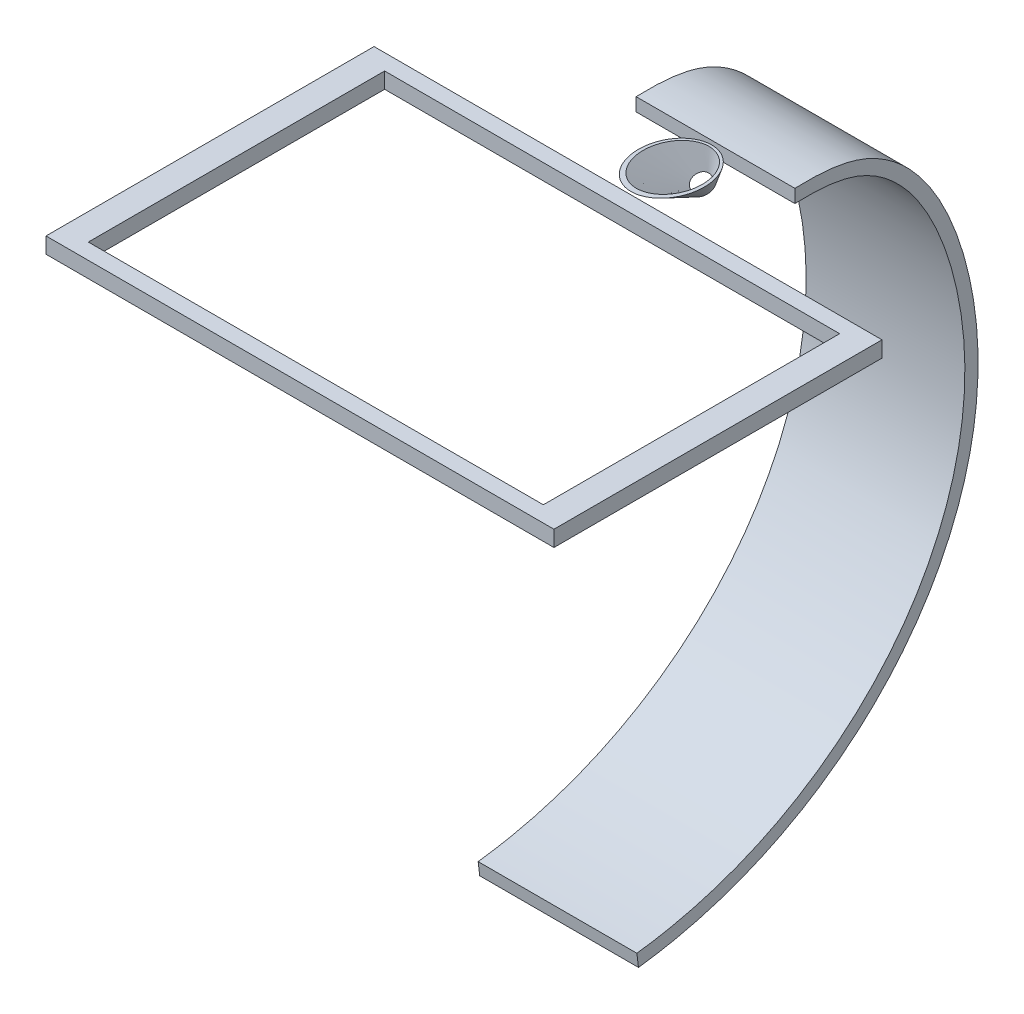
SolidWorks part; units mm, degrees
ref_plane "Front" through (0, 0, 0) normal (0, 0, 1) x (1, 0, 0)
ref_plane "Top" through (0, 0, 0) normal (0, 1, 0) x (1, 0, 0)
ref_plane "Right" through (0, 0, 0) normal (1, 0, 0) x (0, 0, -1)
sketch "Sketch1" plane through (0, 0, 0) normal (0, 1, 0) x (1, 0, 0)
  line L1 (-43, -28) -> (43, -28)
  line L2 (-43, -28) -> (-43, 28)
  line L3 (-43, 28) -> (43, 28)
  line L4 (43, -28) -> (43, 28)
  line L5 (-43, -28) -> (43, 28) construction
  line L6 (-43, 28) -> (43, -28) construction
  line L7 (-48, -31) -> (48, -31)
  line L8 (-48, -31) -> (-48, 31)
  line L9 (-48, 31) -> (48, 31)
  line L10 (48, -31) -> (48, 31)
  line L11 (-48, -31) -> (48, 31) construction
  line L12 (-48, 31) -> (48, -31) construction
  point P0 (0, 0)
  point P6 (0, 0)
  dimension "D1" = 86
  dimension "D2" = 56
  dimension "D3" = 3
  dimension "D4" = 5
extrude "Boss-Extrude1" add sketch "Sketch1" along normal blind 3
sketch "Sketch4" plane through (0, 0, 0) normal (1, 0, 0) x (0, 0, -1)
  line L0 (45.6947, -3.6988) -> (-61.4431, 55.6887) construction
  line L1 (45.6947, -3.6988) -> (-61.4431, 55.6887) construction
  line L2 (32.8171, -9.0552) -> (52.2183, 2.1461) construction
  line L3 (32.8171, -9.0552) -> (52.2183, 2.1461) construction
  line L4 (45.6947, -3.6988) -> (47.8326, 118.7791) construction
  line L5 (45.6947, -3.6988) -> (47.8326, 118.7791) construction
sketch "Sketch5" plane through (0, 0, 0) normal (1, 0, 0) x (0, 0, -1)
  line L0 (45.6947, -3.6988) -> (38.2413, 9.211) construction
  line L1 (32.8171, -9.0552) -> (52.2183, 2.1461) construction
  line L2 (45.6947, -3.6988) -> (-61.4431, 55.6887) construction
  line L3 (43.8581, -2.6807) -> (35.4738, 1.9668)
  line L4 (43.8581, -2.6807) -> (35.4738, 1.9668)
  line L7 (42.8478, -3.264) -> (29.3973, 4.1917)
  line L8 (29.3973, 4.1917) -> (35.4738, 1.9668)
  line L9 (42.8478, -3.264) -> (43.8581, -2.6807)
  line L10 (43.6157, -3.118) -> (32.4355, 3.0793)
  line L11 (43.6157, -3.118) -> (35.2314, 1.5295) construction
  dimension "D1" = 0.5
  dimension "D2" = 0.5
revolve "Revolve4" add sketch "Sketch5" angle 360 about L0 region at (0, 0.2658, -36.9777)
sketch "Sketch6" plane through (0, 0, -31) normal (0, 0, -1) x (-1, 0, 0)
  line L1 (48, 3) -> (-48, 3)
  line L2 (48, 3) -> (48, 16.2937)
  line L3 (48, 16.2937) -> (-48, 16.2937)
  line L4 (-48, 0) -> (48, 0)
  line L5 (48, 0) -> (48, 3)
  line L6 (48, 3) -> (-48, 3)
  line L7 (-48, 3) -> (-48, 0)
  line L8 (-48, 0) -> (48, 0)
  line L9 (48, 0) -> (48, 3)
  line L10 (48, 3) -> (-48, 3)
  line L11 (-48, 3) -> (-48, 0)
  line L12 (-48, 3) -> (-48, 16.2937)
  line M7 (48, 3) -> (-48, 3)
  dimension "D1" = 0
extrude "Cut-Extrude1" cut sketch "Sketch6" along normal through all and the other way through all contours L12 L2 L3 M7 region at (0, 9.6469, -31)
sketch "Sketch7" plane through (0, 0, 0) normal (1, 0, 0) x (0, 0, -1)
  line L13 (32.8171, -19.124) -> (32.8171, -24.1806)
  line L14 (32.8171, -24.1806) -> (37.3171, -21.5825)
  line L15 (37.3171, -21.5825) -> (37.3171, -14.2513)
  line L16 (37.3171, -14.2513) -> (39.4389, -13.0263)
  line L17 (39.4389, -13.0263) -> (38.4389, -11.2943)
  line L18 (38.4389, -11.2943) -> (55.846, -1.2443)
  line L19 (55.846, -1.2443) -> (56.846, -2.9763)
  line L20 (56.846, -2.9763) -> (58.9678, -1.7513)
  line L21 (58.9678, -1.7513) -> (58.5928, -1.1018)
  line L22 (52.2183, 2.1461) -> (32.8171, -9.0552)
  line L23 (32.8171, -9.0552) -> (32.8171, -16.2372)
  line L24 (32.8171, -16.2372) -> (27.8171, -19.124)
  line L25 (27.8171, -19.124) -> (32.8171, -19.124)
  line L26 (32.8171, -19.124) -> (32.8171, -24.1806)
  line L27 (32.8171, -24.1806) -> (37.3171, -21.5825)
  line L28 (37.3171, -21.5825) -> (37.3171, -14.2513)
  line L29 (37.3171, -14.2513) -> (39.4389, -13.0263)
  line L30 (39.4389, -13.0263) -> (38.4389, -11.2943)
  line L31 (38.4389, -11.2943) -> (55.846, -1.2443)
  line L32 (55.846, -1.2443) -> (56.846, -2.9763)
  line L33 (56.846, -2.9763) -> (58.9678, -1.7513)
  line L34 (58.9678, -1.7513) -> (58.5928, -1.1018)
  line L35 (52.2183, 2.1461) -> (32.8171, -9.0552)
  line L36 (32.8171, -9.0552) -> (32.8171, -16.2372)
  line L37 (32.8171, -16.2372) -> (27.8171, -19.124)
  line L38 (27.8171, -19.124) -> (32.8171, -19.124)
  line L53 (58.5928, -1.1018) -> (52.2183, 2.1461)
  line L54 (58.5928, -1.1018) -> (52.2183, 2.1461)
  dimension "D1" = 0
sketch "Sketch8" plane through (0, 0, 0) normal (1, 0, 0) x (0, 0, -1)
  line L2 (46.7417, -1.0158) -> (46.8118, 3) construction
  line L4 (-31, 0) -> (31, 0)
  line L5 (31, 0) -> (31, 3)
  line L6 (31, 3) -> (-31, 3)
  line L7 (-31, 3) -> (-31, 0)
  line L8 (-31, 0) -> (31, 0)
  line L11 (-31, 3) -> (-31, 0)
  line L12 (-35, 7.198) -> (-35, -4)
  line L15 (-31, 2.5) -> (31, 2.5)
  line L16 (47.5312, 3.031) -> (47.5312, 0.5296)
  line L18 (17.6704, -107.2402) -> (17.9773, -109.7213)
  line L25 (-35, -4) -> (31, -4) construction
  line L26 (31, -4) -> (196.6797, -4) construction
  line L29 (31, 0) -> (31.0681, 0) construction
  line L30 (31.0681, 0) -> (-31, 3) construction
  line L31 (196.6797, -4) -> (-35, 7.198) construction
  spline S0 degree 3 poles (31.0681, 0) (39.2616, -0.8727) (64.8569, 6.1362) (83.7032, -33.9651) (74.4322, -82.4857) (41.8152, -104.2537) (17.6704, -107.2402) knots 0 0 0 0 0.161872 0.37793 0.6219 1 1 1 1
  spline S1 degree 1 poles (31.3329, 2.4859) (17.9773, -109.7213) knots 0 0 1 1 construction
  spline S2 degree 3 poles (31.3329, 2.4859) (31.6969, 2.4472) (32.4142, 2.3882) (33.9523, 2.3236) (35.9853, 2.3391) (38.5828, 2.4677) (41.9317, 2.704) (45.4199, 2.961) (49.2514, 3.0962) (53.3847, 3.0159) (57.4792, 2.4307) (61.1315, 1.1545) (64.5235, -0.5792) (68.3029, -3.4951) (73.3809, -9.3848) (78.0753, -18.4595) (81.3839, -30.5483) (82.5085, -42.3505) (81.5804, -53.6922) (78.7417, -64.418) (74.1424, -74.3727) (67.936, -83.4098) (60.2758, -91.3886) (51.3132, -98.1728) (42.8825, -102.7184) (35.6366, -105.6227) (29.9653, -107.4186) (24.0946, -108.8129) (20.0129, -109.4695) (17.9773, -109.7213) knots 0 0 0 0 0.007812 0.015625 0.03125 0.046875 0.0625 0.089111 0.104736 0.125 0.15625 0.171875 0.1875 0.21875 0.25 0.3125 0.375 0.4375 0.5 0.5625 0.625 0.6875 0.75 0.8125 0.875 0.90625 0.9375 0.96875 1 1 1 1
  dimension "D4" = 2.5
  dimension "D1" = 0
  dimension "D2" = 4
  dimension "D3" = 2.5
extrude "Boss-Extrude4" add sketch "Sketch8" along normal blind 15 and the other way blind 15 separate body contours S0 | S2 L16 S0 L18 region at (0, -60.4554, -78.3365)
sketch "Sketch10" plane through (0, 3, 0) normal (0, 1, 0) x (1, 0, 0)
  line L4 (48, -31) -> (48, 31)
  line L5 (48, 31) -> (-48, 31)
  line L6 (-48, 31) -> (-48, -31)
  line L7 (-48, -31) -> (48, -31)
  line L8 (48, -31) -> (48, 31)
  line L9 (48, 31) -> (-48, 31)
  line L10 (-48, 31) -> (-48, -31)
  line L11 (-48, -31) -> (48, -31)
  dimension "D1" = 0
